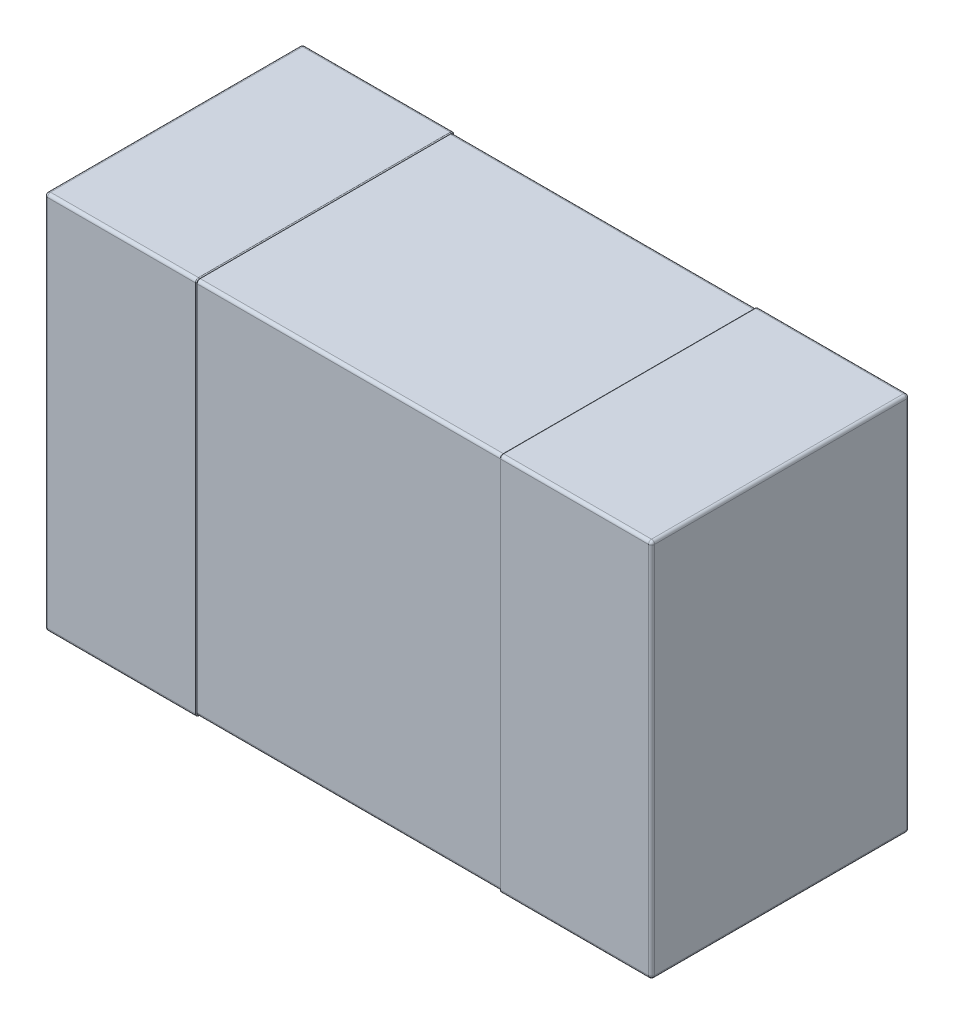
SolidWorks part; units mm, degrees
ref_plane "Top Plane" through (0, 0, 0) normal (0, 0, 1) x (1, 0, 0)
ref_plane "Front Plane" through (0, 0, 0) normal (0, 1, 0) x (1, 0, 0)
ref_plane "Side Plane" through (0, 0, 0) normal (1, 0, 0) x (0, 0, -1)
sketch "Sketch1" plane through (0, 0, 0) normal (0, 0, 1) x (1, 0, 0)
  line L1 (-1, 0.625) -> (1, 0.625)
  line L2 (-1, 0.625) -> (-1, -0.625)
  line L3 (-1, -0.625) -> (1, -0.625)
  line L4 (1, 0.625) -> (1, -0.625)
  dimension "D1" = 2
  dimension "D2" = 1
  dimension "D3" = 1.25
  dimension "D4" = 0.625
extrude "All body" add sketch "Sketch1" along normal blind 0.85
sketch "Sketch2" plane through (0, 0, 0) normal (1, 0, 0) x (0, 0, -1)
  line L14 (-0.003, 0.622) -> (-0.847, 0.622)
  line L15 (-0.003, -0.622) -> (-0.003, 0.622)
  line L16 (-0.847, -0.622) -> (-0.003, -0.622)
  line L17 (-0.847, 0.622) -> (-0.847, -0.622)
  line L18 (-0.003, 0.622) -> (-0.847, 0.622)
  line L19 (-0.003, -0.622) -> (-0.003, 0.622)
  line L20 (-0.847, -0.622) -> (-0.003, -0.622)
  line L21 (-0.847, 0.622) -> (-0.847, -0.622)
  dimension "D1" = 0.003
extrude "Cut out the body for pin" cut sketch "Sketch2" against normal blind 0.5 and the other way blind 0.5 flip side to cut
fillet "Body fillet" radius 0.01 4 edges at (0, 0.622, 0.003) (0, 0.622, 0.847) (0, -0.622, 0.003) (0, -0.622, 0.847)
fillet "Pin fillet a" radius 0.01 16 edges at (1, -0.625, 0.425) (1, 0, 0.85) (1, 0.625, 0.425) (1, 0, 0) (-1, 0.625, 0.425) (-1, 0, 0.85) (-1, -0.625, 0.425) (-1, 0, 0) (0.75, 0.625, 0.85) (0.75, -0.625, 0.85) (0.75, -0.625, 0) (0.75, 0.625, 0) (-0.75, 0.625, 0) (-0.75, -0.625, 0) (-0.75, 0.625, 0.85) (-0.75, -0.625, 0.85)
fillet "Pin fillet b" radius 0.003 16 edges at (0.5, -0.6221, 0.8471) (0.5, -0.625, 0.425) (0.5, -0.6221, 0.0029) (0.5, 0, 0) (0.5, 0.6221, 0.0029) (0.5, 0.625, 0.425) (0.5, 0.6221, 0.8471) (-0.5, -0.6221, 0.8471) (-0.5, -0.625, 0.425) (-0.5, -0.6221, 0.0029) (-0.5, 0, 0) (-0.5, 0.6221, 0.0029) (-0.5, 0.625, 0.425) (-0.5, 0.6221, 0.8471) (0.5, 0, 0.85) (-0.5, 0, 0.85)
